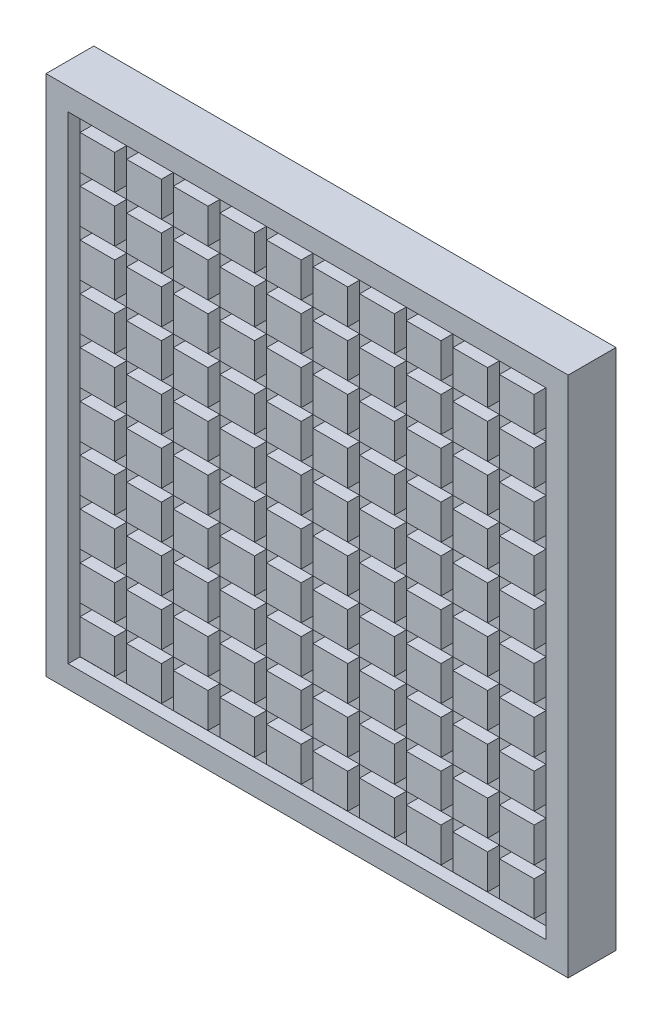
SolidWorks part; units mm, degrees
ref_plane "前视基准面" through (0, 0, 0) normal (0, 0, 1) x (1, 0, 0)
ref_plane "上视基准面" through (0, 0, 0) normal (0, 1, 0) x (1, 0, 0)
ref_plane "右视基准面" through (0, 0, 0) normal (1, 0, 0) x (0, 0, -1)
other "Configuration Table"
sketch "草图1" plane through (0, 0, 0) normal (0, 0, 1) x (1, 0, 0)
  line L1 (0, 0) -> (437, 0)
  line L2 (0, 0) -> (0, 437)
  line L3 (0, 437) -> (437, 437)
  line L4 (437, 0) -> (437, 437)
extrude "凸台-拉伸1" add sketch "草图1" along normal blind 40
ref_point "点2"
sketch "草图2" plane through (0, 0, 0) normal (-1, 0, 0) x (0, 0, 1)
  line L0 (20, 218.5) -> (8.3215, 218.5)
ref_axis "基准轴1" through (0, 218.5, 20) along (0, 0, -1)
ref_axis "基准轴2" through (0, 218.5, 20) along (-1, 0, 0)
sketch "草图3" plane through (0, 0, 40) normal (0, 0, 1) x (1, 0, 0)
  line L25 (18.5, 418.5) -> (418.5, 418.5)
  line L26 (18.5, 418.5) -> (18.5, 18.5)
  line L27 (18.5, 18.5) -> (418.5, 18.5)
  line L28 (418.5, 418.5) -> (418.5, 18.5)
extrude "切除-拉伸1" cut sketch "草图3" against normal blind 10
sketch "草图4" plane through (0, 0, 30) normal (0, 0, 1) x (1, 0, 0)
  line L0 (67.5, 408.6283) -> (67.5, 379.6283)
  line L5 (28.5, 408.6283) -> (57.5, 408.6283)
  line L6 (28.5, 408.6283) -> (28.5, 379.6283)
  line L7 (28.5, 379.6283) -> (57.5, 379.6283)
  line L8 (57.5, 408.6283) -> (57.5, 379.6283)
  line L9 (67.5, 408.6283) -> (96.5, 408.6283)
  line L10 (96.5, 408.6283) -> (96.5, 379.6283)
  line L11 (67.5, 379.6283) -> (96.5, 379.6283)
  line L12 (106.5, 408.6283) -> (106.5, 379.6283)
  line L13 (106.5, 408.6283) -> (135.5, 408.6283)
  line L14 (135.5, 408.6283) -> (135.5, 379.6283)
  line L15 (106.5, 379.6283) -> (135.5, 379.6283)
  line L16 (145.5, 408.6283) -> (145.5, 379.6283)
  line L17 (145.5, 408.6283) -> (174.5, 408.6283)
  line L18 (174.5, 408.6283) -> (174.5, 379.6283)
  line L19 (145.5, 379.6283) -> (174.5, 379.6283)
  line L20 (184.5, 408.6283) -> (184.5, 379.6283)
  line L21 (184.5, 408.6283) -> (213.5, 408.6283)
  line L22 (213.5, 408.6283) -> (213.5, 379.6283)
  line L23 (184.5, 379.6283) -> (213.5, 379.6283)
  line L24 (223.5, 408.6283) -> (223.5, 379.6283)
  line L25 (223.5, 408.6283) -> (252.5, 408.6283)
  line L26 (252.5, 408.6283) -> (252.5, 379.6283)
  line L27 (223.5, 379.6283) -> (252.5, 379.6283)
  line L28 (262.5, 408.6283) -> (262.5, 379.6283)
  line L29 (262.5, 408.6283) -> (291.5, 408.6283)
  line L30 (291.5, 408.6283) -> (291.5, 379.6283)
  line L31 (262.5, 379.6283) -> (291.5, 379.6283)
  line L32 (301.5, 408.6283) -> (301.5, 379.6283)
  line L33 (301.5, 408.6283) -> (330.5, 408.6283)
  line L34 (330.5, 408.6283) -> (330.5, 379.6283)
  line L35 (301.5, 379.6283) -> (330.5, 379.6283)
  line L36 (340.5, 408.6283) -> (340.5, 379.6283)
  line L37 (340.5, 408.6283) -> (369.5, 408.6283)
  line L38 (369.5, 408.6283) -> (369.5, 379.6283)
  line L39 (340.5, 379.6283) -> (369.5, 379.6283)
  line L40 (379.5, 408.6283) -> (379.5, 379.6283)
  line L41 (379.5, 408.6283) -> (408.5, 408.6283)
  line L42 (408.5, 408.6283) -> (408.5, 379.6283)
  line L43 (379.5, 379.6283) -> (408.5, 379.6283)
  line L44 (67.5, 369.6283) -> (67.5, 340.6283)
  line L45 (67.5, 369.6283) -> (96.5, 369.6283)
  line L46 (96.5, 369.6283) -> (96.5, 340.6283)
  line L47 (67.5, 340.6283) -> (96.5, 340.6283)
  line L48 (106.5, 369.6283) -> (106.5, 340.6283)
  line L49 (106.5, 369.6283) -> (135.5, 369.6283)
  line L50 (135.5, 369.6283) -> (135.5, 340.6283)
  line L51 (106.5, 340.6283) -> (135.5, 340.6283)
  line L52 (145.5, 369.6283) -> (145.5, 340.6283)
  line L53 (145.5, 369.6283) -> (174.5, 369.6283)
  line L54 (174.5, 369.6283) -> (174.5, 340.6283)
  line L55 (145.5, 340.6283) -> (174.5, 340.6283)
  line L56 (184.5, 369.6283) -> (184.5, 340.6283)
  line L57 (184.5, 369.6283) -> (213.5, 369.6283)
  line L58 (213.5, 369.6283) -> (213.5, 340.6283)
  line L59 (184.5, 340.6283) -> (213.5, 340.6283)
  line L60 (223.5, 369.6283) -> (223.5, 340.6283)
  line L61 (223.5, 369.6283) -> (252.5, 369.6283)
  line L62 (252.5, 369.6283) -> (252.5, 340.6283)
  line L63 (223.5, 340.6283) -> (252.5, 340.6283)
  line L64 (262.5, 369.6283) -> (262.5, 340.6283)
  line L65 (262.5, 369.6283) -> (291.5, 369.6283)
  line L66 (291.5, 369.6283) -> (291.5, 340.6283)
  line L67 (262.5, 340.6283) -> (291.5, 340.6283)
  line L68 (301.5, 369.6283) -> (301.5, 340.6283)
  line L69 (301.5, 369.6283) -> (330.5, 369.6283)
  line L70 (330.5, 369.6283) -> (330.5, 340.6283)
  line L71 (301.5, 340.6283) -> (330.5, 340.6283)
  line L72 (340.5, 369.6283) -> (340.5, 340.6283)
  line L73 (340.5, 369.6283) -> (369.5, 369.6283)
  line L74 (369.5, 369.6283) -> (369.5, 340.6283)
  line L75 (340.5, 340.6283) -> (369.5, 340.6283)
  line L76 (379.5, 369.6283) -> (379.5, 340.6283)
  line L77 (379.5, 369.6283) -> (408.5, 369.6283)
  line L78 (408.5, 369.6283) -> (408.5, 340.6283)
  line L79 (379.5, 340.6283) -> (408.5, 340.6283)
  line L80 (67.5, 330.6283) -> (67.5, 301.6283)
  line L81 (67.5, 330.6283) -> (96.5, 330.6283)
  line L82 (96.5, 330.6283) -> (96.5, 301.6283)
  line L83 (67.5, 301.6283) -> (96.5, 301.6283)
  line L84 (106.5, 330.6283) -> (106.5, 301.6283)
  line L85 (106.5, 330.6283) -> (135.5, 330.6283)
  line L86 (135.5, 330.6283) -> (135.5, 301.6283)
  line L87 (106.5, 301.6283) -> (135.5, 301.6283)
  line L88 (145.5, 330.6283) -> (145.5, 301.6283)
  line L89 (145.5, 330.6283) -> (174.5, 330.6283)
  line L90 (174.5, 330.6283) -> (174.5, 301.6283)
  line L91 (145.5, 301.6283) -> (174.5, 301.6283)
  line L92 (184.5, 330.6283) -> (184.5, 301.6283)
  line L93 (184.5, 330.6283) -> (213.5, 330.6283)
  line L94 (213.5, 330.6283) -> (213.5, 301.6283)
  line L95 (184.5, 301.6283) -> (213.5, 301.6283)
  line L96 (223.5, 330.6283) -> (223.5, 301.6283)
  line L97 (223.5, 330.6283) -> (252.5, 330.6283)
  line L98 (252.5, 330.6283) -> (252.5, 301.6283)
  line L99 (223.5, 301.6283) -> (252.5, 301.6283)
  line L100 (262.5, 330.6283) -> (262.5, 301.6283)
  line L101 (262.5, 330.6283) -> (291.5, 330.6283)
  line L102 (291.5, 330.6283) -> (291.5, 301.6283)
  line L103 (262.5, 301.6283) -> (291.5, 301.6283)
  line L104 (301.5, 330.6283) -> (301.5, 301.6283)
  line L105 (301.5, 330.6283) -> (330.5, 330.6283)
  line L106 (330.5, 330.6283) -> (330.5, 301.6283)
  line L107 (301.5, 301.6283) -> (330.5, 301.6283)
  line L108 (340.5, 330.6283) -> (340.5, 301.6283)
  line L109 (340.5, 330.6283) -> (369.5, 330.6283)
  line L110 (369.5, 330.6283) -> (369.5, 301.6283)
  line L111 (340.5, 301.6283) -> (369.5, 301.6283)
  line L112 (379.5, 330.6283) -> (379.5, 301.6283)
  line L113 (379.5, 330.6283) -> (408.5, 330.6283)
  line L114 (408.5, 330.6283) -> (408.5, 301.6283)
  line L115 (379.5, 301.6283) -> (408.5, 301.6283)
  line L116 (67.5, 291.6283) -> (67.5, 262.6283)
  line L117 (67.5, 291.6283) -> (96.5, 291.6283)
  line L118 (96.5, 291.6283) -> (96.5, 262.6283)
  line L119 (67.5, 262.6283) -> (96.5, 262.6283)
  line L120 (106.5, 291.6283) -> (106.5, 262.6283)
  line L121 (106.5, 291.6283) -> (135.5, 291.6283)
  line L122 (135.5, 291.6283) -> (135.5, 262.6283)
  line L123 (106.5, 262.6283) -> (135.5, 262.6283)
  line L124 (145.5, 291.6283) -> (145.5, 262.6283)
  line L125 (145.5, 291.6283) -> (174.5, 291.6283)
  line L126 (174.5, 291.6283) -> (174.5, 262.6283)
  line L127 (145.5, 262.6283) -> (174.5, 262.6283)
  line L128 (184.5, 291.6283) -> (184.5, 262.6283)
  line L129 (184.5, 291.6283) -> (213.5, 291.6283)
  line L130 (213.5, 291.6283) -> (213.5, 262.6283)
  line L131 (184.5, 262.6283) -> (213.5, 262.6283)
  line L132 (223.5, 291.6283) -> (223.5, 262.6283)
  line L133 (223.5, 291.6283) -> (252.5, 291.6283)
  line L134 (252.5, 291.6283) -> (252.5, 262.6283)
  line L135 (223.5, 262.6283) -> (252.5, 262.6283)
  line L136 (262.5, 291.6283) -> (262.5, 262.6283)
  line L137 (262.5, 291.6283) -> (291.5, 291.6283)
  line L138 (291.5, 291.6283) -> (291.5, 262.6283)
  line L139 (262.5, 262.6283) -> (291.5, 262.6283)
  line L140 (301.5, 291.6283) -> (301.5, 262.6283)
  line L141 (301.5, 291.6283) -> (330.5, 291.6283)
  line L142 (330.5, 291.6283) -> (330.5, 262.6283)
  line L143 (301.5, 262.6283) -> (330.5, 262.6283)
  line L144 (340.5, 291.6283) -> (340.5, 262.6283)
  line L145 (340.5, 291.6283) -> (369.5, 291.6283)
  line L146 (369.5, 291.6283) -> (369.5, 262.6283)
  line L147 (340.5, 262.6283) -> (369.5, 262.6283)
  line L148 (379.5, 291.6283) -> (379.5, 262.6283)
  line L149 (379.5, 291.6283) -> (408.5, 291.6283)
  line L150 (408.5, 291.6283) -> (408.5, 262.6283)
  line L151 (379.5, 262.6283) -> (408.5, 262.6283)
  line L152 (67.5, 252.6283) -> (67.5, 223.6283)
  line L153 (67.5, 252.6283) -> (96.5, 252.6283)
  line L154 (96.5, 252.6283) -> (96.5, 223.6283)
  line L155 (67.5, 223.6283) -> (96.5, 223.6283)
  line L156 (106.5, 252.6283) -> (106.5, 223.6283)
  line L157 (106.5, 252.6283) -> (135.5, 252.6283)
  line L158 (135.5, 252.6283) -> (135.5, 223.6283)
  line L159 (106.5, 223.6283) -> (135.5, 223.6283)
  line L160 (145.5, 252.6283) -> (145.5, 223.6283)
  line L161 (145.5, 252.6283) -> (174.5, 252.6283)
  line L162 (174.5, 252.6283) -> (174.5, 223.6283)
  line L163 (145.5, 223.6283) -> (174.5, 223.6283)
  line L164 (184.5, 252.6283) -> (184.5, 223.6283)
  line L165 (184.5, 252.6283) -> (213.5, 252.6283)
  line L166 (213.5, 252.6283) -> (213.5, 223.6283)
  line L167 (184.5, 223.6283) -> (213.5, 223.6283)
  line L168 (223.5, 252.6283) -> (223.5, 223.6283)
  line L169 (223.5, 252.6283) -> (252.5, 252.6283)
  line L170 (252.5, 252.6283) -> (252.5, 223.6283)
  line L171 (223.5, 223.6283) -> (252.5, 223.6283)
  line L172 (262.5, 252.6283) -> (262.5, 223.6283)
  line L173 (262.5, 252.6283) -> (291.5, 252.6283)
  line L174 (291.5, 252.6283) -> (291.5, 223.6283)
  line L175 (262.5, 223.6283) -> (291.5, 223.6283)
  line L176 (301.5, 252.6283) -> (301.5, 223.6283)
  line L177 (301.5, 252.6283) -> (330.5, 252.6283)
  line L178 (330.5, 252.6283) -> (330.5, 223.6283)
  line L179 (301.5, 223.6283) -> (330.5, 223.6283)
  line L180 (340.5, 252.6283) -> (340.5, 223.6283)
  line L181 (340.5, 252.6283) -> (369.5, 252.6283)
  line L182 (369.5, 252.6283) -> (369.5, 223.6283)
  line L183 (340.5, 223.6283) -> (369.5, 223.6283)
  line L184 (379.5, 252.6283) -> (379.5, 223.6283)
  line L185 (379.5, 252.6283) -> (408.5, 252.6283)
  line L186 (408.5, 252.6283) -> (408.5, 223.6283)
  line L187 (379.5, 223.6283) -> (408.5, 223.6283)
  line L188 (67.5, 213.6283) -> (67.5, 184.6283)
  line L189 (67.5, 213.6283) -> (96.5, 213.6283)
  line L190 (96.5, 213.6283) -> (96.5, 184.6283)
  line L191 (67.5, 184.6283) -> (96.5, 184.6283)
  line L192 (106.5, 213.6283) -> (106.5, 184.6283)
  line L193 (106.5, 213.6283) -> (135.5, 213.6283)
  line L194 (135.5, 213.6283) -> (135.5, 184.6283)
  line L195 (106.5, 184.6283) -> (135.5, 184.6283)
  line L196 (145.5, 213.6283) -> (145.5, 184.6283)
  line L197 (145.5, 213.6283) -> (174.5, 213.6283)
  line L198 (174.5, 213.6283) -> (174.5, 184.6283)
  line L199 (145.5, 184.6283) -> (174.5, 184.6283)
  line L200 (184.5, 213.6283) -> (184.5, 184.6283)
  line L201 (184.5, 213.6283) -> (213.5, 213.6283)
  line L202 (213.5, 213.6283) -> (213.5, 184.6283)
  line L203 (184.5, 184.6283) -> (213.5, 184.6283)
  line L204 (223.5, 213.6283) -> (223.5, 184.6283)
  line L205 (223.5, 213.6283) -> (252.5, 213.6283)
  line L206 (252.5, 213.6283) -> (252.5, 184.6283)
  line L207 (223.5, 184.6283) -> (252.5, 184.6283)
  line L208 (262.5, 213.6283) -> (262.5, 184.6283)
  line L209 (262.5, 213.6283) -> (291.5, 213.6283)
  line L210 (291.5, 213.6283) -> (291.5, 184.6283)
  line L211 (262.5, 184.6283) -> (291.5, 184.6283)
  line L212 (301.5, 213.6283) -> (301.5, 184.6283)
  line L213 (301.5, 213.6283) -> (330.5, 213.6283)
  line L214 (330.5, 213.6283) -> (330.5, 184.6283)
  line L215 (301.5, 184.6283) -> (330.5, 184.6283)
  line L216 (340.5, 213.6283) -> (340.5, 184.6283)
  line L217 (340.5, 213.6283) -> (369.5, 213.6283)
  line L218 (369.5, 213.6283) -> (369.5, 184.6283)
  line L219 (340.5, 184.6283) -> (369.5, 184.6283)
  line L220 (379.5, 213.6283) -> (379.5, 184.6283)
  line L221 (379.5, 213.6283) -> (408.5, 213.6283)
  line L222 (408.5, 213.6283) -> (408.5, 184.6283)
  line L223 (379.5, 184.6283) -> (408.5, 184.6283)
  line L224 (67.5, 174.6283) -> (67.5, 145.6283)
  line L225 (67.5, 174.6283) -> (96.5, 174.6283)
  line L226 (96.5, 174.6283) -> (96.5, 145.6283)
  line L227 (67.5, 145.6283) -> (96.5, 145.6283)
  line L228 (106.5, 174.6283) -> (106.5, 145.6283)
  line L229 (106.5, 174.6283) -> (135.5, 174.6283)
  line L230 (135.5, 174.6283) -> (135.5, 145.6283)
  line L231 (106.5, 145.6283) -> (135.5, 145.6283)
  line L232 (145.5, 174.6283) -> (145.5, 145.6283)
  line L233 (145.5, 174.6283) -> (174.5, 174.6283)
  line L234 (174.5, 174.6283) -> (174.5, 145.6283)
  line L235 (145.5, 145.6283) -> (174.5, 145.6283)
  line L236 (184.5, 174.6283) -> (184.5, 145.6283)
  line L237 (184.5, 174.6283) -> (213.5, 174.6283)
  line L238 (213.5, 174.6283) -> (213.5, 145.6283)
  line L239 (184.5, 145.6283) -> (213.5, 145.6283)
  line L240 (223.5, 174.6283) -> (223.5, 145.6283)
  line L241 (223.5, 174.6283) -> (252.5, 174.6283)
  line L242 (252.5, 174.6283) -> (252.5, 145.6283)
  line L243 (223.5, 145.6283) -> (252.5, 145.6283)
  line L244 (262.5, 174.6283) -> (262.5, 145.6283)
  line L245 (262.5, 174.6283) -> (291.5, 174.6283)
  line L246 (291.5, 174.6283) -> (291.5, 145.6283)
  line L247 (262.5, 145.6283) -> (291.5, 145.6283)
  line L248 (301.5, 174.6283) -> (301.5, 145.6283)
  line L249 (301.5, 174.6283) -> (330.5, 174.6283)
  line L250 (330.5, 174.6283) -> (330.5, 145.6283)
  line L251 (301.5, 145.6283) -> (330.5, 145.6283)
  line L252 (340.5, 174.6283) -> (340.5, 145.6283)
  line L253 (340.5, 174.6283) -> (369.5, 174.6283)
  line L254 (369.5, 174.6283) -> (369.5, 145.6283)
  line L255 (340.5, 145.6283) -> (369.5, 145.6283)
  line L256 (379.5, 174.6283) -> (379.5, 145.6283)
  line L257 (379.5, 174.6283) -> (408.5, 174.6283)
  line L258 (408.5, 174.6283) -> (408.5, 145.6283)
  line L259 (379.5, 145.6283) -> (408.5, 145.6283)
  line L260 (67.5, 135.6283) -> (67.5, 106.6283)
  line L261 (67.5, 135.6283) -> (96.5, 135.6283)
  line L262 (96.5, 135.6283) -> (96.5, 106.6283)
  line L263 (67.5, 106.6283) -> (96.5, 106.6283)
  line L264 (106.5, 135.6283) -> (106.5, 106.6283)
  line L265 (106.5, 135.6283) -> (135.5, 135.6283)
  line L266 (135.5, 135.6283) -> (135.5, 106.6283)
  line L267 (106.5, 106.6283) -> (135.5, 106.6283)
  line L268 (145.5, 135.6283) -> (145.5, 106.6283)
  line L269 (145.5, 135.6283) -> (174.5, 135.6283)
  line L270 (174.5, 135.6283) -> (174.5, 106.6283)
  line L271 (145.5, 106.6283) -> (174.5, 106.6283)
  line L272 (184.5, 135.6283) -> (184.5, 106.6283)
  line L273 (184.5, 135.6283) -> (213.5, 135.6283)
  line L274 (213.5, 135.6283) -> (213.5, 106.6283)
  line L275 (184.5, 106.6283) -> (213.5, 106.6283)
  line L276 (223.5, 135.6283) -> (223.5, 106.6283)
  line L277 (223.5, 135.6283) -> (252.5, 135.6283)
  line L278 (252.5, 135.6283) -> (252.5, 106.6283)
  line L279 (223.5, 106.6283) -> (252.5, 106.6283)
  line L280 (262.5, 135.6283) -> (262.5, 106.6283)
  line L281 (262.5, 135.6283) -> (291.5, 135.6283)
  line L282 (291.5, 135.6283) -> (291.5, 106.6283)
  line L283 (262.5, 106.6283) -> (291.5, 106.6283)
  line L284 (301.5, 135.6283) -> (301.5, 106.6283)
  line L285 (301.5, 135.6283) -> (330.5, 135.6283)
  line L286 (330.5, 135.6283) -> (330.5, 106.6283)
  line L287 (301.5, 106.6283) -> (330.5, 106.6283)
  line L288 (340.5, 135.6283) -> (340.5, 106.6283)
  line L289 (340.5, 135.6283) -> (369.5, 135.6283)
  line L290 (369.5, 135.6283) -> (369.5, 106.6283)
  line L291 (340.5, 106.6283) -> (369.5, 106.6283)
  line L292 (379.5, 135.6283) -> (379.5, 106.6283)
  line L293 (379.5, 135.6283) -> (408.5, 135.6283)
  line L294 (408.5, 135.6283) -> (408.5, 106.6283)
  line L295 (379.5, 106.6283) -> (408.5, 106.6283)
  line L296 (67.5, 96.6283) -> (67.5, 67.6283)
  line L297 (67.5, 96.6283) -> (96.5, 96.6283)
  line L298 (96.5, 96.6283) -> (96.5, 67.6283)
  line L299 (67.5, 67.6283) -> (96.5, 67.6283)
  line L300 (106.5, 96.6283) -> (106.5, 67.6283)
  line L301 (106.5, 96.6283) -> (135.5, 96.6283)
  line L302 (135.5, 96.6283) -> (135.5, 67.6283)
  line L303 (106.5, 67.6283) -> (135.5, 67.6283)
  line L304 (145.5, 96.6283) -> (145.5, 67.6283)
  line L305 (145.5, 96.6283) -> (174.5, 96.6283)
  line L306 (174.5, 96.6283) -> (174.5, 67.6283)
  line L307 (145.5, 67.6283) -> (174.5, 67.6283)
  line L308 (184.5, 96.6283) -> (184.5, 67.6283)
  line L309 (184.5, 96.6283) -> (213.5, 96.6283)
  line L310 (213.5, 96.6283) -> (213.5, 67.6283)
  line L311 (184.5, 67.6283) -> (213.5, 67.6283)
  line L312 (223.5, 96.6283) -> (223.5, 67.6283)
  line L313 (223.5, 96.6283) -> (252.5, 96.6283)
  line L314 (252.5, 96.6283) -> (252.5, 67.6283)
  line L315 (223.5, 67.6283) -> (252.5, 67.6283)
  line L316 (262.5, 96.6283) -> (262.5, 67.6283)
  line L317 (262.5, 96.6283) -> (291.5, 96.6283)
  line L318 (291.5, 96.6283) -> (291.5, 67.6283)
  line L319 (262.5, 67.6283) -> (291.5, 67.6283)
  line L320 (301.5, 96.6283) -> (301.5, 67.6283)
  line L321 (301.5, 96.6283) -> (330.5, 96.6283)
  line L322 (330.5, 96.6283) -> (330.5, 67.6283)
  line L323 (301.5, 67.6283) -> (330.5, 67.6283)
  line L324 (340.5, 96.6283) -> (340.5, 67.6283)
  line L325 (340.5, 96.6283) -> (369.5, 96.6283)
  line L326 (369.5, 96.6283) -> (369.5, 67.6283)
  line L327 (340.5, 67.6283) -> (369.5, 67.6283)
  line L328 (379.5, 96.6283) -> (379.5, 67.6283)
  line L329 (379.5, 96.6283) -> (408.5, 96.6283)
  line L330 (408.5, 96.6283) -> (408.5, 67.6283)
  line L331 (379.5, 67.6283) -> (408.5, 67.6283)
  line L332 (67.5, 57.6283) -> (67.5, 28.6283)
  line L333 (67.5, 57.6283) -> (96.5, 57.6283)
  line L334 (96.5, 57.6283) -> (96.5, 28.6283)
  line L335 (67.5, 28.6283) -> (96.5, 28.6283)
  line L336 (106.5, 57.6283) -> (106.5, 28.6283)
  line L337 (106.5, 57.6283) -> (135.5, 57.6283)
  line L338 (135.5, 57.6283) -> (135.5, 28.6283)
  line L339 (106.5, 28.6283) -> (135.5, 28.6283)
  line L340 (145.5, 57.6283) -> (145.5, 28.6283)
  line L341 (145.5, 57.6283) -> (174.5, 57.6283)
  line L342 (174.5, 57.6283) -> (174.5, 28.6283)
  line L343 (145.5, 28.6283) -> (174.5, 28.6283)
  line L344 (184.5, 57.6283) -> (184.5, 28.6283)
  line L345 (184.5, 57.6283) -> (213.5, 57.6283)
  line L346 (213.5, 57.6283) -> (213.5, 28.6283)
  line L347 (184.5, 28.6283) -> (213.5, 28.6283)
  line L348 (223.5, 57.6283) -> (223.5, 28.6283)
  line L349 (223.5, 57.6283) -> (252.5, 57.6283)
  line L350 (252.5, 57.6283) -> (252.5, 28.6283)
  line L351 (223.5, 28.6283) -> (252.5, 28.6283)
  line L352 (262.5, 57.6283) -> (262.5, 28.6283)
  line L353 (262.5, 57.6283) -> (291.5, 57.6283)
  line L354 (291.5, 57.6283) -> (291.5, 28.6283)
  line L355 (262.5, 28.6283) -> (291.5, 28.6283)
  line L356 (301.5, 57.6283) -> (301.5, 28.6283)
  line L357 (301.5, 57.6283) -> (330.5, 57.6283)
  line L358 (330.5, 57.6283) -> (330.5, 28.6283)
  line L359 (301.5, 28.6283) -> (330.5, 28.6283)
  line L360 (340.5, 57.6283) -> (340.5, 28.6283)
  line L361 (340.5, 57.6283) -> (369.5, 57.6283)
  line L362 (369.5, 57.6283) -> (369.5, 28.6283)
  line L363 (340.5, 28.6283) -> (369.5, 28.6283)
  line L364 (379.5, 57.6283) -> (379.5, 28.6283)
  line L365 (379.5, 57.6283) -> (408.5, 57.6283)
  line L366 (408.5, 57.6283) -> (408.5, 28.6283)
  line L367 (379.5, 28.6283) -> (408.5, 28.6283)
  line L368 (28.5, 369.6283) -> (28.5, 340.6283)
  line L369 (28.5, 369.6283) -> (57.5, 369.6283)
  line L370 (57.5, 369.6283) -> (57.5, 340.6283)
  line L371 (28.5, 340.6283) -> (57.5, 340.6283)
  line L372 (28.5, 330.6283) -> (28.5, 301.6283)
  line L373 (28.5, 330.6283) -> (57.5, 330.6283)
  line L374 (57.5, 330.6283) -> (57.5, 301.6283)
  line L375 (28.5, 301.6283) -> (57.5, 301.6283)
  line L376 (28.5, 291.6283) -> (28.5, 262.6283)
  line L377 (28.5, 291.6283) -> (57.5, 291.6283)
  line L378 (57.5, 291.6283) -> (57.5, 262.6283)
  line L379 (28.5, 262.6283) -> (57.5, 262.6283)
  line L380 (28.5, 252.6283) -> (28.5, 223.6283)
  line L381 (28.5, 252.6283) -> (57.5, 252.6283)
  line L382 (57.5, 252.6283) -> (57.5, 223.6283)
  line L383 (28.5, 223.6283) -> (57.5, 223.6283)
  line L384 (28.5, 213.6283) -> (28.5, 184.6283)
  line L385 (28.5, 213.6283) -> (57.5, 213.6283)
  line L386 (57.5, 213.6283) -> (57.5, 184.6283)
  line L387 (28.5, 184.6283) -> (57.5, 184.6283)
  line L388 (28.5, 174.6283) -> (28.5, 145.6283)
  line L389 (28.5, 174.6283) -> (57.5, 174.6283)
  line L390 (57.5, 174.6283) -> (57.5, 145.6283)
  line L391 (28.5, 145.6283) -> (57.5, 145.6283)
  line L392 (28.5, 135.6283) -> (28.5, 106.6283)
  line L393 (28.5, 135.6283) -> (57.5, 135.6283)
  line L394 (57.5, 135.6283) -> (57.5, 106.6283)
  line L395 (28.5, 106.6283) -> (57.5, 106.6283)
  line L396 (28.5, 96.6283) -> (28.5, 67.6283)
  line L397 (28.5, 96.6283) -> (57.5, 96.6283)
  line L398 (57.5, 96.6283) -> (57.5, 67.6283)
  line L399 (28.5, 67.6283) -> (57.5, 67.6283)
  line L400 (28.5, 57.6283) -> (28.5, 28.6283)
  line L401 (28.5, 57.6283) -> (57.5, 57.6283)
  line L402 (57.5, 57.6283) -> (57.5, 28.6283)
  line L403 (28.5, 28.6283) -> (57.5, 28.6283)
  dimension "D1" = 10
  dimension "D2" = 10
extrude "凸台-拉伸2" add sketch "草图4" along normal blind 10
scale "缩放比例1" scale about centroid uniform scaling yes scale factor 0.94089
